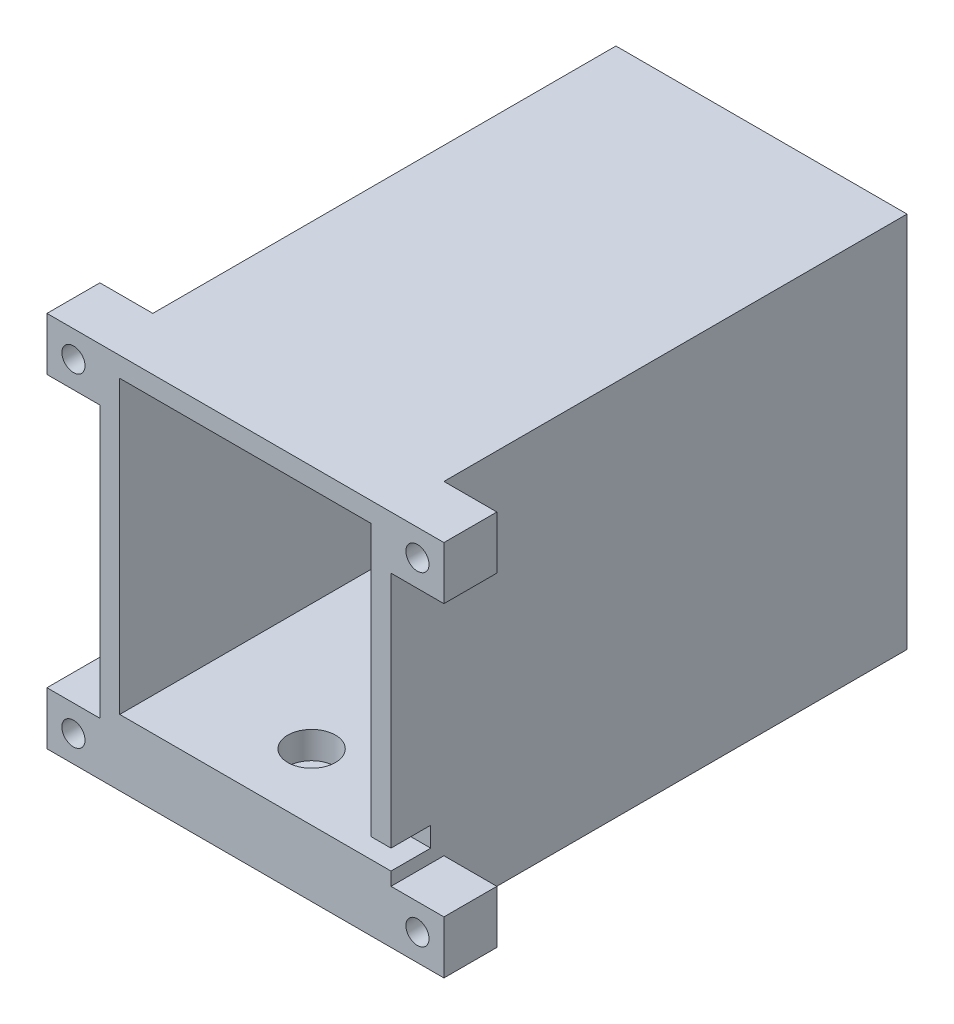
SolidWorks part; units mm, degrees
ref_plane "前基準面" through (0, 0, 0) normal (0, 0, 1) x (1, 0, 0)
ref_plane "上基準面" through (0, 0, 0) normal (0, 1, 0) x (1, 0, 0)
ref_plane "右基準面" through (0, 0, 0) normal (1, 0, 0) x (0, 0, -1)
sketch "草圖1" plane through (0, 0, 0) normal (0, 1, 0) x (1, 0, 0)
  line L1 (-22, 39) -> (22, 39)
  line L2 (-22, 39) -> (-22, -39)
  line L3 (-22, -39) -> (22, -39)
  line L4 (22, 39) -> (22, -39)
  line L5 (-22, 39) -> (22, -39) construction
  line L6 (-22, -39) -> (22, 39) construction
  point P0 (0, 0)
  dimension "D1" = 78
  dimension "D2" = 44
extrude "填料-伸長1" add sketch "草圖1" along normal blind 57
shell "薄殼1" thickness 3 removed face at (0, 28.5, 39)
sketch "草圖3" plane through (0, 10, 0) normal (0, 1, 0) x (1, 0, 0)
  line L0 (-22, -39) -> (22, -39) construction
  circle A0 centre (0, 25) radius 3.6
  circle A1 centre (0, -29) radius 3.6
  dimension "D1" = 7.2
  dimension "D2" = 54
  dimension "D3" = 10
extrude "除料-伸長1" cut sketch "草圖3" against normal blind 4.1
sketch "草圖4" plane through (0, 10, 0) normal (0, 1, 0) x (1, 0, 0)
  circle A0 centre (0, 25) radius 2.25
  circle A1 centre (0, -29) radius 2.25
  dimension "D1" = 4.5
extrude "除料-伸長2" cut sketch "草圖4" against normal up to next
sketch "草圖5" plane through (0, 0, 39) normal (0, 0, 1) x (1, 0, 0)
  line L0 (22, 57) -> (22, 0) construction
  line L1 (19, 10) -> (22, 10)
  line L2 (19, 10) -> (19, 13)
  line L3 (19, 13) -> (22, 13)
  line L4 (22, 10) -> (22, 13)
  dimension "D1" = 3
extrude "除料-伸長3" cut sketch "草圖5" against normal blind 6
sketch "草圖6" plane through (0, 0, 39) normal (0, 0, 1) x (1, 0, 0)
  line L0 (-22, 57) -> (-22, 0) construction
  line L1 (-30, 49) -> (-22, 49)
  line L2 (-30, 49) -> (-30, 57)
  line L3 (-30, 57) -> (-22, 57)
  line L4 (-22, 49) -> (-22, 57)
  line L5 (-30, 49) -> (-22, 57) construction
  line L6 (-30, 57) -> (-22, 49) construction
  line L7 (-30, 8) -> (-22, 8)
  line L8 (-30, 8) -> (-30, 0)
  line L9 (-30, 0) -> (-22, 0)
  line L10 (-22, 8) -> (-22, 0)
  line L11 (-30, 8) -> (-22, 0) construction
  line L12 (-30, 0) -> (-22, 8) construction
  line L13 (0, 0) -> (0, 16.0157) construction
  line L14 (30, 0) -> (22, 8) construction
  line L15 (30, 8) -> (22, 0) construction
  line L16 (30, 57) -> (22, 49) construction
  line L17 (30, 49) -> (22, 57) construction
  line L18 (22, 8) -> (22, 0)
  line L19 (30, 0) -> (22, 0)
  line L20 (30, 8) -> (30, 0)
  line L21 (30, 8) -> (22, 8)
  line L22 (22, 49) -> (22, 57)
  line L23 (30, 57) -> (22, 57)
  line L24 (30, 49) -> (30, 57)
  line L25 (30, 49) -> (22, 49)
  circle A0 centre (-26, 53) radius 1.75
  circle A1 centre (-26, 4) radius 1.75
  circle A2 centre (26, 4) radius 1.75
  circle A3 centre (26, 53) radius 1.75
  point P0 (-26, 53)
  point P6 (-26, 4)
  point P25 (26, 4)
  point P26 (26, 53)
  dimension "D3" = 3.5
  dimension "D1" = 8
  dimension "D2" = 8
extrude "填料-伸長2" add sketch "草圖6" against normal blind 8
sketch "草圖7" plane through (0, 0, 31) normal (0, 0, -1) x (-1, 0, 0)
  line L0 (0, 0) -> (0, 13.0726) construction
  line L1 (-22.8246, 53) -> (-24.4123, 55.75)
  line L2 (-24.4123, 55.75) -> (-27.5877, 55.75)
  line L3 (-27.5877, 55.75) -> (-29.1754, 53)
  line L4 (-29.1754, 53) -> (-27.5877, 50.25)
  line L5 (-27.5877, 50.25) -> (-24.4123, 50.25)
  line L6 (-24.4123, 50.25) -> (-22.8246, 53)
  line L7 (-22.8246, 4) -> (-24.4123, 6.75)
  line L8 (-24.4123, 6.75) -> (-27.5877, 6.75)
  line L9 (-27.5877, 6.75) -> (-29.1754, 4)
  line L10 (-29.1754, 4) -> (-27.5877, 1.25)
  line L11 (-27.5877, 1.25) -> (-24.4123, 1.25)
  line L12 (-24.4123, 1.25) -> (-22.8246, 4)
  line L13 (24.4123, 1.25) -> (22.8246, 4)
  line L14 (27.5877, 1.25) -> (24.4123, 1.25)
  line L15 (29.1754, 4) -> (27.5877, 1.25)
  line L16 (27.5877, 6.75) -> (29.1754, 4)
  line L17 (24.4123, 6.75) -> (27.5877, 6.75)
  line L18 (22.8246, 4) -> (24.4123, 6.75)
  line L19 (24.4123, 50.25) -> (22.8246, 53)
  line L20 (27.5877, 50.25) -> (24.4123, 50.25)
  line L21 (29.1754, 53) -> (27.5877, 50.25)
  line L22 (27.5877, 55.75) -> (29.1754, 53)
  line L23 (24.4123, 55.75) -> (27.5877, 55.75)
  line L24 (22.8246, 53) -> (24.4123, 55.75)
  circle A0 centre (-26, 53) radius 2.75 construction
  circle A1 centre (-26, 4) radius 2.75 construction
  circle A2 centre (26, 4) radius 2.75 construction
  circle A3 centre (26, 53) radius 2.75 construction
  dimension "D1" = 5.5
extrude "除料-伸長4" cut sketch "草圖7" against normal blind 2.6
